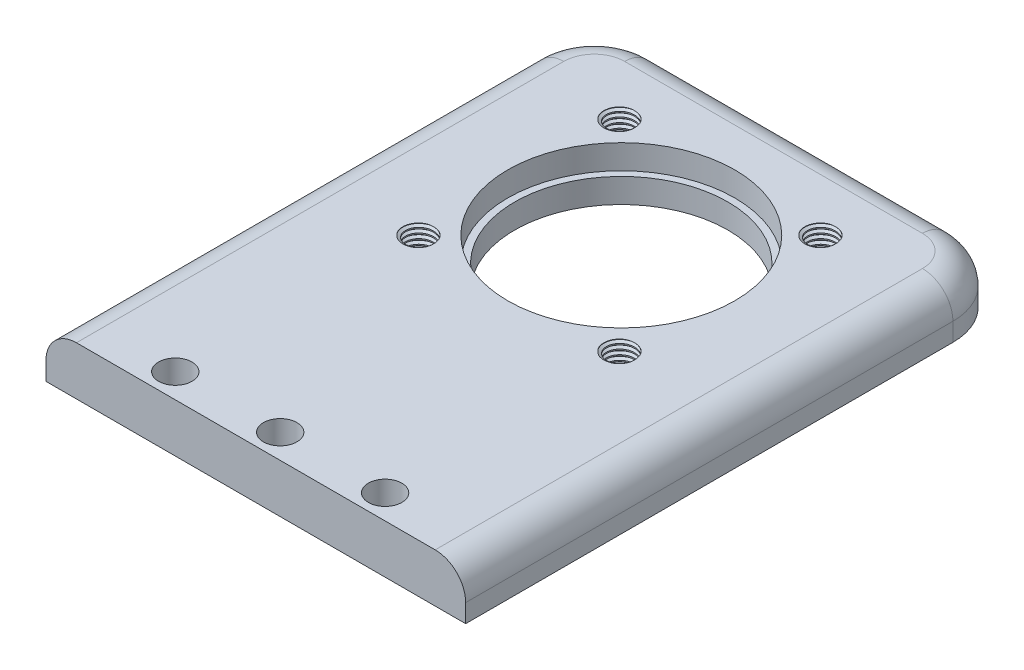
SolidWorks part; units mm, degrees
ref_plane "Front Plane" through (0, 0, 0) normal (0, 0, 1) x (1, 0, 0)
ref_plane "Top Plane" through (0, 0, 0) normal (0, 1, 0) x (1, 0, 0)
ref_plane "Right Plane" through (0, 0, 0) normal (1, 0, 0) x (0, 0, -1)
sketch "Sketch1" plane through (0, 0, 0) normal (0, 1, 0) x (1, 0, 0)
  line L1 (0, 0) -> (68.9, 0)
  line L2 (0, 0) -> (0, 90)
  line L3 (0, 90) -> (68.9, 90)
  line L4 (68.9, 0) -> (68.9, 90)
  circle A0 centre (34.45, 60) radius 18.63
  circle A1 centre (34.45, 4) radius 2.75
  circle A2 centre (17.225, 4) radius 2.75
  circle A3 centre (51.675, 4) radius 2.75
  dimension "D3" = 34.45
  dimension "D5" = 34.45
  dimension "D8" = 4
  dimension "D1" = 68.9
  dimension "D2" = 90
  dimension "D4" = 30
  dimension "D6" = 17.225
  dimension "D7" = 17.225
extrude "Boss-Extrude1" add sketch "Sketch1" along normal blind 8
fillet "Fillet1" radius 10 2 edges at (68.9, 4, -90) (0, 4, -90)
fillet "Fillet2" radius 5 5 edges at (65.9711, 8, -87.0711) (34.45, 8, -90) (2.9289, 8, -87.0711) (68.9, 8, -40) (0, 8, -40)
sketch "Sketch2" plane through (0, 0, 0) normal (0, -1, 0) x (1, 0, 0)
  circle A0 centre (34.45, -60) radius 18.63
  circle A1 centre (34.45, -60) radius 17.5
extrude "Boss-Extrude2" add sketch "Sketch2" against normal blind 4
sketch "Sketch5" plane through (0, 8, 0) normal (0, 1, 0) x (1, 0, 0)
  line L1 (50.95, 43.5) -> (17.95, 43.5)
  line L2 (50.95, 43.5) -> (50.95, 76.5)
  line L3 (50.95, 76.5) -> (17.95, 76.5)
  line L4 (17.95, 43.5) -> (17.95, 76.5)
  line L5 (50.95, 43.5) -> (17.95, 76.5) construction
  line L6 (50.95, 76.5) -> (17.95, 43.5) construction
  circle A0 centre (17.95, 76.5) radius 2.3
  circle A1 centre (50.95, 76.5) radius 2.3
  circle A2 centre (50.95, 43.5) radius 2.3
  circle A3 centre (17.95, 43.5) radius 2.3
  point P0 (34.45, 60)
  dimension "D1" = 33
  dimension "D2" = 33
extrude "Cut-Extrude1" cut sketch "Sketch5" against normal blind 6 contours L3 A0 L4 | L4 A0 L3 | L2 A1 L3 | L1 A2 L2 | L4 A3 L1 | L1 A3 L4 | L2 A2 L1 region at (17.6246, 8, -43.1746) region at (18.9262, 8, -44.4762) region at (49.9738, 8, -44.4762) region at (51.2754, 8, -43.1746) region at (17.6246, 8, -76.8254) region at (18.9262, 8, -75.5238) region at (51.2754, 8, -76.8254)
thread "Thread1" pitch 0.8 method cut profile "Thread Profile1" start angle 0, offset 1, length 0, pitch 0.8, diameter 4.6
ref_plane "Plane1" through (15.65, 9, -76.5) normal (0, 0, 1) x (-1, 0, 0)
sketch "Thread Profile1" plane through (15.65, 9, -76.5) normal (0, 0, 1) x (-1, 0, 0)
  line L0 (0, 0) -> (0, 0.8) construction
  line L1 (0, 0) -> (0.433, 0.25)
  line L2 (0.433, 0.25) -> (0.433, 0.35)
  line L3 (0.433, 0.35) -> (0, 0.6)
  line L4 (0.433, 0.3) -> (0, 0.3) construction
  line L11 (0, 0) -> (0, 0.6)
  point P2 (0, 0)
  dimension "Pitch" = 0.8
  dimension "Profile_Angle" = 60
  dimension "Profile_Land" = 0.1
  dimension "Profile_Height" = 0.433
thread "Thread2" pitch 0.8 method cut profile "Thread Profile2" start angle 0, offset 1, length 0, pitch 0.8, diameter 4.6
ref_plane "Plane2" through (48.65, 9, -43.5) normal (0, 0, 1) x (-1, 0, 0)
sketch "Thread Profile2" plane through (48.65, 9, -43.5) normal (0, 0, 1) x (-1, 0, 0)
  line L0 (0, 0) -> (0, 0.8) construction
  line L1 (0, 0) -> (0.433, 0.25)
  line L2 (0.433, 0.25) -> (0.433, 0.35)
  line L3 (0.433, 0.35) -> (0, 0.6)
  line L4 (0.433, 0.3) -> (0, 0.3) construction
  line L11 (0, 0) -> (0, 0.6)
  point P2 (0, 0)
  dimension "Pitch" = 0.8
  dimension "Profile_Angle" = 60
  dimension "Profile_Land" = 0.1
  dimension "Profile_Height" = 0.433
thread "Thread3" pitch 0.8 method cut profile "Thread Profile3" start angle 0, offset 1, length 0, pitch 0.8, diameter 4.6
ref_plane "Plane3" through (15.65, 9, -43.5) normal (0, 0, 1) x (-1, 0, 0)
sketch "Thread Profile3" plane through (15.65, 9, -43.5) normal (0, 0, 1) x (-1, 0, 0)
  line L0 (0, 0) -> (0, 0.8) construction
  line L1 (0, 0) -> (0.433, 0.25)
  line L2 (0.433, 0.25) -> (0.433, 0.35)
  line L3 (0.433, 0.35) -> (0, 0.6)
  line L4 (0.433, 0.3) -> (0, 0.3) construction
  line L11 (0, 0) -> (0, 0.6)
  point P2 (0, 0)
  dimension "Pitch" = 0.8
  dimension "Profile_Angle" = 60
  dimension "Profile_Land" = 0.1
  dimension "Profile_Height" = 0.433
extrude "Cut-Extrude2" cut sketch "Sketch5<3>" against normal blind 6 contours L3 A1 L2 region at (49.9738, 8, -75.5238)
sketch "Sketch5<3>" plane through (0, 8, 0) normal (0, 1, 0) x (1, 0, 0) same geometry as "Sketch5"
thread "Thread4" pitch 0.8 method cut profile "Thread Profile4" start angle 0, offset 1, length 0, pitch 0.8, diameter 4.6
ref_plane "Plane4" through (48.65, 9, -76.5) normal (0, 0, 1) x (-1, 0, 0)
sketch "Thread Profile4" plane through (48.65, 9, -76.5) normal (0, 0, 1) x (-1, 0, 0)
  line L0 (0, 0) -> (0, 0.8) construction
  line L1 (0, 0) -> (0.433, 0.25)
  line L2 (0.433, 0.25) -> (0.433, 0.35)
  line L3 (0.433, 0.35) -> (0, 0.6)
  line L4 (0.433, 0.3) -> (0, 0.3) construction
  line L11 (0, 0) -> (0, 0.6)
  point P2 (0, 0)
  dimension "Pitch" = 0.8
  dimension "Profile_Angle" = 60
  dimension "Profile_Land" = 0.1
  dimension "Profile_Height" = 0.433
sketch "Sketch14" plane through (0, 8, 0) normal (0, 1, 0) x (1, 0, 0)
  circle A0 centre (34.45, 60) radius 23.3345
